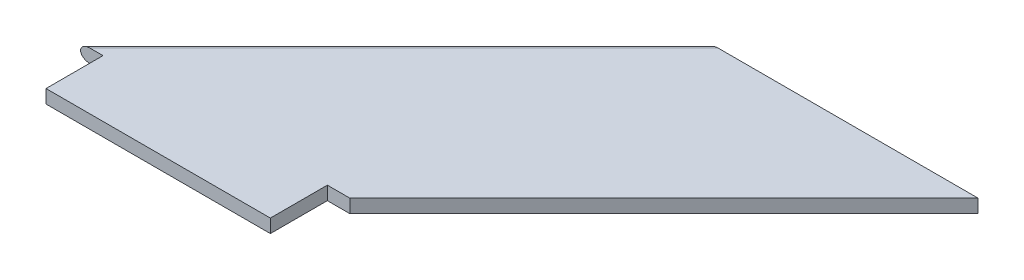
SolidWorks part; units mm, degrees
ref_plane "Front Plane" through (0, 0, 0) normal (0, 0, 1) x (1, 0, 0)
ref_plane "Top Plane" through (0, 0, 0) normal (0, 1, 0) x (1, 0, 0)
ref_plane "Right Plane" through (0, 0, 0) normal (1, 0, 0) x (0, 0, -1)
sketch "Sketch1" plane through (0, 0, 0) normal (0, 1, 0) x (1, 0, 0)
  line L0 (0, 0) -> (70, 70)
  line L1 (70, 70) -> (130, 70)
  line L2 (130, 70) -> (60, 0)
  line L3 (60, 0) -> (55, 0)
  line L4 (55, 0) -> (55, -12.7)
  line L5 (55, -12.7) -> (5, -12.7)
  line L6 (5, -12.7) -> (5, 0)
  line L7 (5, 0) -> (0, 0)
  dimension "D1" = 50
  dimension "D2" = 12.7
  dimension "D3" = 70
  dimension "D4" = 70
  dimension "D5" = 130
  dimension "D6" = 60
extrude "Boss-Extrude2" add sketch "Sketch1" along normal blind 3
fillet "Fillet1" radius 1.5 2 edges at (35, 3, -35) (35, 0, -35)
